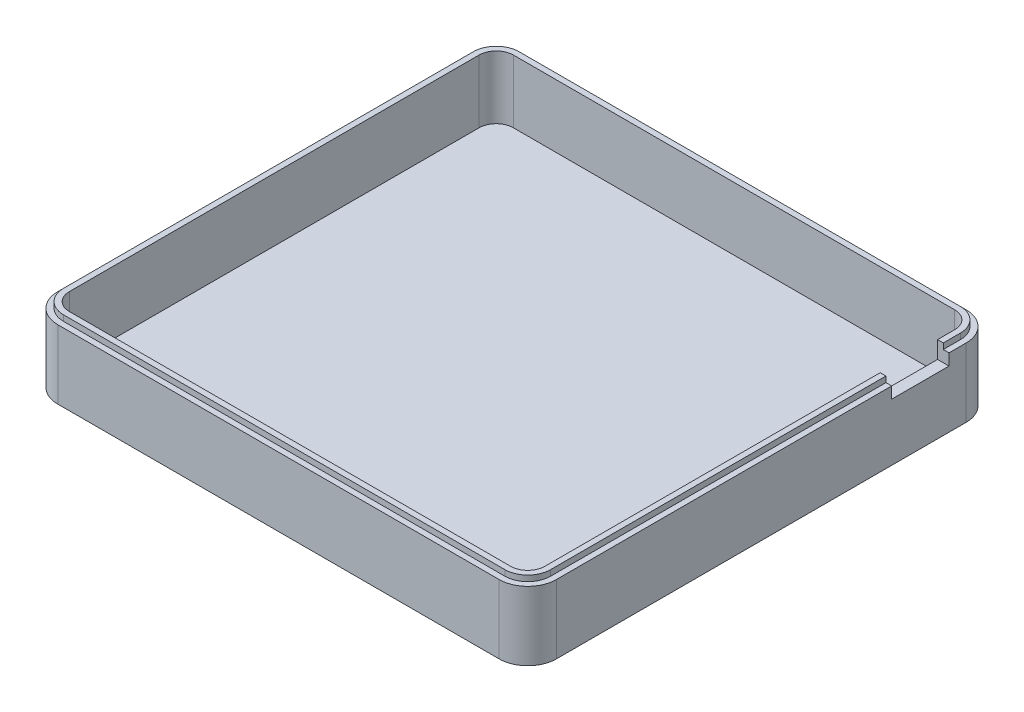
SolidWorks part; units mm, degrees
ref_plane "Спереди" through (0, 0, 0) normal (0, 0, 1) x (1, 0, 0)
ref_plane "Сверху" through (0, 0, 0) normal (0, 1, 0) x (1, 0, 0)
ref_plane "Справа" through (0, 0, 0) normal (1, 0, 0) x (0, 0, -1)
other "Configuration Table"
sketch "Эскиз1" plane through (0, 0, 0) normal (0, 1, 0) x (1, 0, 0)
  line L0 (41.4156, 1.5506) -> (41.4156, -75.9494)
  line L1 (2.9156, 1.5506) -> (79.9156, 1.5506) construction
  line L2 (-0.0844, -1.4494) -> (-0.0844, -72.9494) construction
  line L3 (2.9156, -75.9494) -> (79.9156, -75.9494) construction
  line L4 (82.9156, -1.4494) -> (82.9156, -72.9494) construction
  line L5 (-0.0844, -37.1994) -> (82.9156, -37.1994)
  line L6 (-2.0844, -1.4494) -> (-2.0844, -72.9494)
  line L7 (2.9156, -77.9494) -> (79.9156, -77.9494)
  line L8 (84.9156, -1.4494) -> (84.9156, -72.9494)
  line L9 (2.9156, 3.5506) -> (79.9156, 3.5506)
  line L10 (-0.0844, -1.4494) -> (-0.0844, -72.9494)
  line L11 (2.9156, -75.9494) -> (79.9156, -75.9494)
  line L12 (82.9156, -1.4494) -> (82.9156, -72.9494)
  line L13 (2.9156, 1.5506) -> (79.9156, 1.5506)
  circle A0 centre (9.9156, -65.9494) radius 3.9775
  circle A1 centre (9.9156, -8.4494) radius 3.9775
  circle A2 centre (72.9156, -8.4494) radius 3.9775
  circle A3 centre (72.9156, -65.9494) radius 3.9775
  arc A4 (79.9156, -75.9494) -> (82.9156, -72.9494) centre (79.9156, -72.9494) ccw construction
  arc A5 (79.9156, 1.5506) -> (82.9156, -1.4494) centre (79.9156, -1.4494) cw construction
  arc A6 (2.9156, 1.5506) -> (-0.0844, -1.4494) centre (2.9156, -1.4494) ccw construction
  arc A7 (-0.0844, -72.9494) -> (2.9156, -75.9494) centre (2.9156, -72.9494) ccw construction
  arc A8 (-2.0844, -72.9494) -> (2.9156, -77.9494) centre (2.9156, -72.9494) ccw
  arc A9 (79.9156, -77.9494) -> (84.9156, -72.9494) centre (79.9156, -72.9494) ccw
  arc A10 (79.9156, 3.5506) -> (84.9156, -1.4494) centre (79.9156, -1.4494) cw
  arc A11 (2.9156, 3.5506) -> (-2.0844, -1.4494) centre (2.9156, -1.4494) ccw
  arc A12 (-0.0844, -72.9494) -> (2.9156, -75.9494) centre (2.9156, -72.9494) ccw
  arc A13 (79.9156, -75.9494) -> (82.9156, -72.9494) centre (79.9156, -72.9494) ccw
  arc A14 (79.9156, 1.5506) -> (82.9156, -1.4494) centre (79.9156, -1.4494) cw
  arc A15 (2.9156, 1.5506) -> (-0.0844, -1.4494) centre (2.9156, -1.4494) ccw
  point P20 (82.9156, 1.5506)
  point P23 (-0.0844, 1.5506)
  point P26 (-0.0844, -75.9494)
  dimension "D3" = 10
  dimension "D5" = 3
  dimension "D1" = 83
  dimension "D2" = 77.5
  dimension "D4" = 10
extrude "Бобышка-Вытянуть4" add sketch "Эскиз1" along normal blind 2 contours L6 A8 L7 A9 L8 A10 L9 A11
extrude "Бобышка-Вытянуть5" add sketch "Эскиз1<9>" along normal blind 12 contours L6 A8 L7 A9 L8 A10 L9 A11 | L10 A12 L11 A13 L12 A14 L13 A15
sketch "Эскиз1<9>" plane through (0, 0, 0) normal (0, 1, 0) x (1, 0, 0) same geometry as "Эскиз1"
sketch "Эскиз3" plane through (0, 0, 0) normal (0, -1, 0) x (1, 0, 0)
  line L12 (2.9156, -2.5506) -> (79.9156, -2.5506)
  line L13 (83.9156, 1.4494) -> (83.9156, 72.9494)
  line L14 (79.9156, 76.9494) -> (2.9156, 76.9494)
  line L15 (-1.0844, 72.9494) -> (-1.0844, 1.4494)
  line L16 (2.9156, -2.5506) -> (79.9156, -2.5506)
  line L17 (83.9156, 1.4494) -> (83.9156, 72.9494)
  line L18 (79.9156, 76.9494) -> (2.9156, 76.9494)
  line L19 (-1.0844, 72.9494) -> (-1.0844, 1.4494)
  arc A12 (-1.0844, 1.4494) -> (2.9156, -2.5506) centre (2.9156, 1.4494) ccw
  arc A13 (79.9156, -2.5506) -> (83.9156, 1.4494) centre (79.9156, 1.4494) ccw
  arc A14 (83.9156, 72.9494) -> (79.9156, 76.9494) centre (79.9156, 72.9494) ccw
  arc A15 (2.9156, 76.9494) -> (-1.0844, 72.9494) centre (2.9156, 72.9494) ccw
  arc A16 (-1.0844, 1.4494) -> (2.9156, -2.5506) centre (2.9156, 1.4494) ccw
  arc A17 (79.9156, -2.5506) -> (83.9156, 1.4494) centre (79.9156, 1.4494) ccw
  arc A18 (83.9156, 72.9494) -> (79.9156, 76.9494) centre (79.9156, 72.9494) ccw
  arc A19 (2.9156, 76.9494) -> (-1.0844, 72.9494) centre (2.9156, 72.9494) ccw
  dimension "D1" = 1
extrude "Бобышка-Вытянуть7" add sketch "Эскиз3" against normal blind 1 from surface contours L18 A19 L19 A16 L16 A17 L17 A18 starting at face at (41.4156, 12, 37.1994)
extrude "Вырез-Вытянуть4" cut sketch "Эскиз1<13>" against normal blind 11 from surface contours L13 A14 L12 A13 L11 A12 L10 A15 starting at face at (41.4156, 13, 37.1994)
sketch "Эскиз1<13>" plane through (0, 0, 0) normal (0, 1, 0) x (1, 0, 0) same geometry as "Эскиз1"
sketch "Эскиз4" plane through (84.9156, 0, 0) normal (1, 0, 0) x (0, 0, -1)
  line L0 (-1.4494, 0) -> (-72.9494, 0) construction
  line L1 (-14.4494, 15) -> (-4.4494, 15)
  line L2 (-14.4494, 15) -> (-14.4494, 10)
  line L3 (-14.4494, 10) -> (-4.4494, 10)
  line L4 (-4.4494, 15) -> (-4.4494, 10)
  line L6 (3.5506, 12) -> (3.5506, 0) construction
  dimension "D1" = 10
  dimension "D2" = 5
  dimension "D3" = 10
  dimension "D4" = 8
extrude "Вырез-Вытянуть5" cut sketch "Эскиз4" against normal up to next
